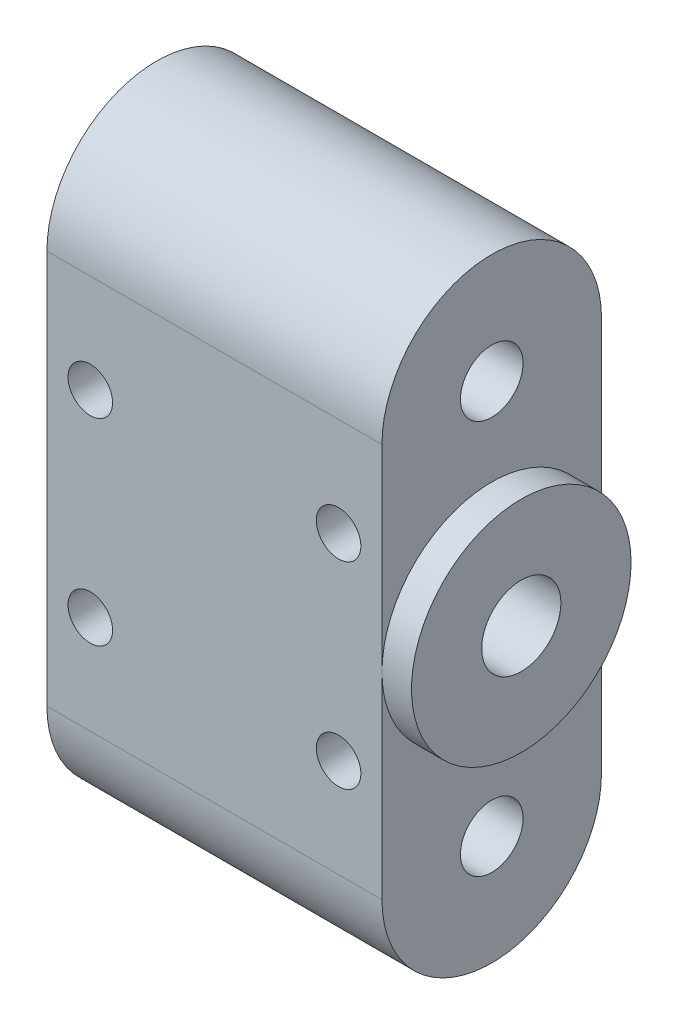
SolidWorks part; units mm, degrees
ref_plane "Front" through (0, 0, 0) normal (0, 0, 1) x (1, 0, 0)
ref_plane "Top" through (0, 0, 0) normal (0, 1, 0) x (1, 0, 0)
ref_plane "Right" through (0, 0, 0) normal (1, 0, 0) x (0, 0, -1)
sketch "Sketch1" plane through (0, 0, 0) normal (1, 0, 0) x (0, 0, -1)
  line L0 (0, 12.7) -> (0, -12.7) construction
  line L1 (7.0739, 12.7) -> (7.0739, -12.7)
  line L2 (-7.0739, 12.7) -> (-7.0739, -12.7)
  arc A0 (7.0739, 12.7) -> (-7.0739, 12.7) centre (0, 12.7) ccw
  arc A1 (-7.0739, -12.7) -> (7.0739, -12.7) centre (0, -12.7) ccw
  point P2 (0, 0)
  dimension "D1" = 14.1478
  dimension "D2" = 25.4
extrude "Boss-Extrude1" add sketch "Sketch1" along normal blind 21.59
sketch "Sketch8" plane through (21.59, 0, 0) normal (1, 0, 0) x (0, 0, -1)
  circle A0 centre (0, 0) radius 7.0739
  dimension "D1" = 14.1478
extrude "Boss-Extrude2" add sketch "Sketch8" along normal blind 1.905
hole_wizard "1/4-20 Tapped Hole1" positions "Sketch9" profile "Sketch10" tap size "1/4-20" standard "ANSI Inch" end condition through all
sketch "Sketch9" plane through (23.495, 0, 0) normal (1, 0, 0) x (0, 0, -1)
  point P0 (0, 0)
sketch "Sketch10" plane through (23.495, 0, 0) normal (0, 1, 0) x (0, 0, -1)
  line L0 (0, 0) -> (0, 23.495)
  line L1 (0, 23.495) -> (2.5527, 23.495)
  line L2 (2.5527, 23.495) -> (2.5527, 0)
  line L5 (2.5527, 0) -> (0, 0)
  line L11 (0, -6.35) -> (0, 107.95) construction
  dimension "Thru Tap Drill Dia." = 5.1054
  dimension "Thru Tap Drill Depth" = 23.495
cosmetic thread "Hole Thread8" parameters "D2"=6.35
hole_wizard "#10-32 Tapped Hole1" positions "Sketch4" profile "Sketch5" tap size "#10-32" standard "ANSI Inch" end condition through all
sketch "Sketch4" plane through (21.59, 0, 0) normal (1, 0, 0) x (0, 0, -1)
  point P0 (0, 12.7)
  point P2 (0, -12.7)
sketch "Sketch5" plane through (21.59, 12.7, 0) normal (0, 1, 0) x (0, 0, -1)
  line L0 (0, 0) -> (0, 21.59)
  line L1 (0, 21.59) -> (2.0193, 21.59)
  line L2 (2.0193, 21.59) -> (2.0193, 0)
  line L5 (2.0193, 0) -> (0, 0)
  line L11 (0, -6.35) -> (0, 107.95) construction
  dimension "Thru Tap Drill Dia." = 4.0386
  dimension "Thru Tap Drill Depth" = 21.59
cosmetic thread "Hole Thread2" parameters "D2"=4.826
cosmetic thread "Hole Thread3" parameters "D2"=4.826
hole_wizard "#6-40 Tapped Hole1" positions "Sketch6" profile "Sketch7" tap size "#6-40" standard "ANSI Inch" end condition through all
sketch "Sketch6" plane through (0, 0, 7.0739) normal (0, 0, 1) x (1, 0, 0)
  line L5 (2.795, 6.35) -> (2.795, -6.35) construction
  line L7 (0, 0) -> (21.59, 0) construction
  line L8 (0, 12.7) -> (0, -12.7) construction
  line L12 (2.795, 6.35) -> (18.795, 6.35) construction
  line L14 (10.795, 6.35) -> (10.795, 0) construction
  line L15 (21.59, 12.7) -> (21.59, 0) construction
  point P0 (2.795, 6.35)
  point P2 (18.795, 6.35)
  point P4 (2.795, -6.35)
  point P6 (18.795, -6.35)
  point P54 (2.795, 0)
  point P56 (0, 0)
  point P57 (0, 0)
  dimension "D1" = 16
  dimension "D2" = 12.7
cosmetic thread "Hole Thread4" parameters "D2"=3.5052
cosmetic thread "Hole Thread5" parameters "D2"=3.5052
cosmetic thread "Hole Thread6" parameters "D2"=3.5052
cosmetic thread "Hole Thread7" parameters "D2"=3.5052
sketch "Sketch7" plane through (2.795, 6.35, 7.0739) normal (1, 0, 0) x (0, -1, 0)
  line L0 (0, 0) -> (0, 14.1478)
  line L1 (0, 14.1478) -> (1.4351, 14.1478)
  line L2 (1.4351, 14.1478) -> (1.4351, 0)
  line L5 (1.4351, 0) -> (0, 0)
  line L11 (0, -6.35) -> (0, 107.95) construction
  dimension "Thru Tap Drill Dia." = 2.8702
  dimension "Thru Tap Drill Depth" = 14.1478
